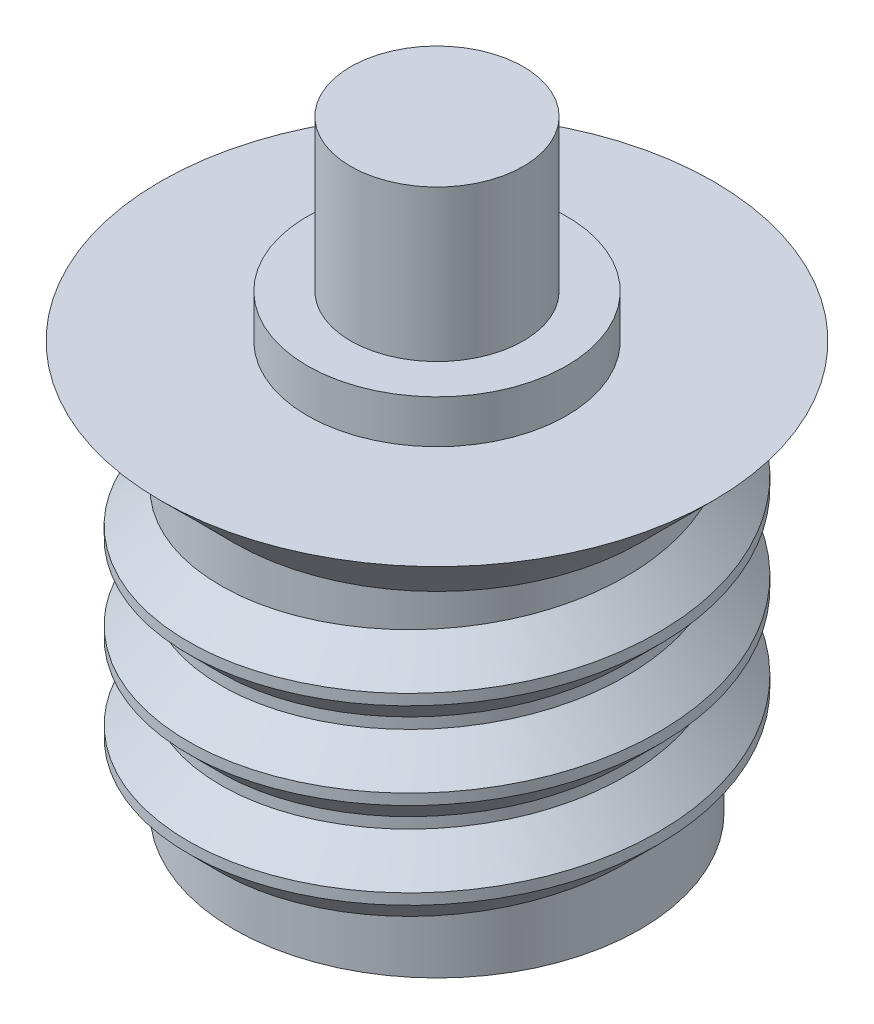
SolidWorks part; units mm, degrees
ref_plane "前视基准面" through (0, 0, 0) normal (0, 0, 1) x (1, 0, 0)
ref_plane "上视基准面" through (0, 0, 0) normal (0, 1, 0) x (1, 0, 0)
ref_plane "右视基准面" through (0, 0, 0) normal (1, 0, 0) x (0, 0, -1)
sketch "草图1" plane through (0, 0, 0) normal (0, 1, 0) x (1, 0, 0)
  circle A0 centre (0, 0) radius 9.4
  dimension "D1" = 18.8
extrude "凸台-拉伸1" add sketch "草图1" along normal blind 15.5
sketch "草图2" plane through (0, 0, 0) normal (0, 0, 1) x (1, 0, 0)
  line L0 (0, 18.9) -> (12.8, 18.9)
  line L1 (9.4, 15.5) -> (-9.4, 15.5) construction
  line L2 (9.4, 15.5) -> (0, 15.5)
  line L3 (9.4, 15.5) -> (12.8, 18.9)
  line L4 (0, 15.5) -> (0, 18.9)
  dimension "D1" = 135
  dimension "D2" = 3.4
revolve "旋转1" add sketch "草图2" angle 360 about L4
sketch "草图3" plane through (0, 18.9, 0) normal (0, 1, 0) x (1, 0, 0)
  circle A0 centre (0, 0) radius 6
  dimension "D1" = 12
extrude "凸台-拉伸2" add sketch "草图3" along normal blind 2
sketch "草图4" plane through (0, 20.9, 0) normal (0, 1, 0) x (1, 0, 0)
  circle A0 centre (0, 0) radius 4
  dimension "D1" = 8
extrude "凸台-拉伸3" add sketch "草图4" along normal blind 7
ref_plane "基准面1" through (0, 1.75, 0) normal (0, -1, 0) x (-1, 0, 0)
sketch "草图7" plane through (0, 1.75, 0) normal (0, -1, 0) x (-1, 0, 0)
  circle A0 centre (0, 0) radius 9.4 construction
  circle A1 centre (0, 0) radius 9.4
curve "螺旋线/涡状线2" pitch 4 height 12 radius 9.4 centre (0, 1.75, 0) axis (0, 1, 0) start towards (0, 0, -1)
sketch "草图8" plane through (0, 0, 0) normal (1, 0, 0) x (0, 0, -1)
  line L0 (9.4, 3.5) -> (9.4, 0)
  line L1 (9.4, 0) -> (10.9, 1.5)
  line L2 (10.9, 1.5) -> (10.9, 2)
  line L3 (10.9, 2) -> (9.4, 3.5)
  point P2 (9.4, 1.75)
  dimension "D1" = 3.5
  dimension "D2" = 1.5
  dimension "D3" = 45
sweep "扫描1" add profiles "草图8" path "螺旋线/涡状线2"
